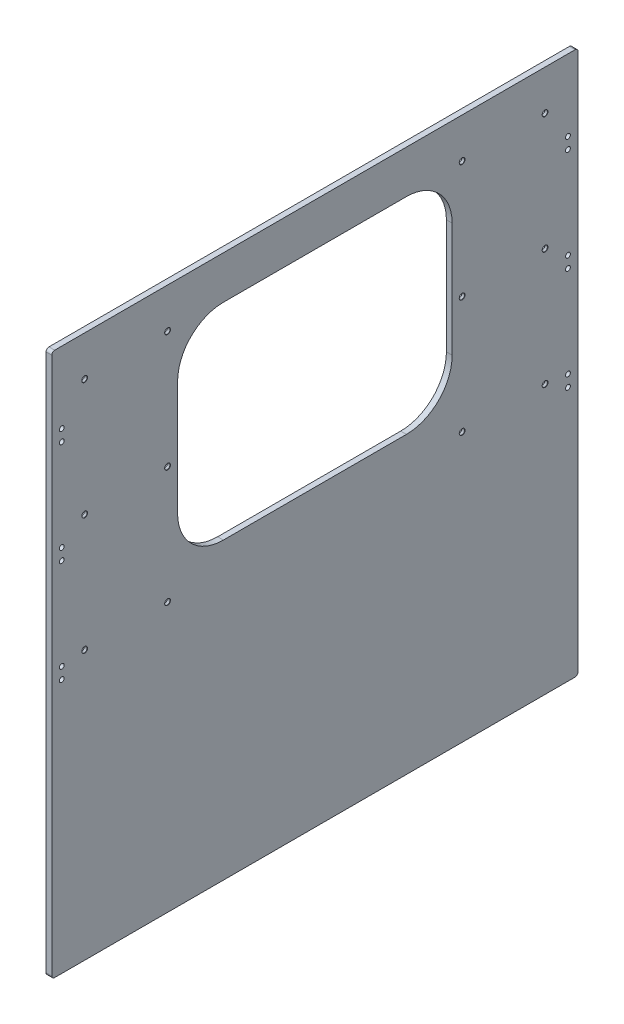
SolidWorks part; units mm, degrees
material "PE High Density"
ref_plane "Front Plane" through (0, 0, 0) normal (0, 0, 1) x (1, 0, 0)
ref_plane "Top Plane" through (0, 0, 0) normal (0, 1, 0) x (1, 0, 0)
ref_plane "Right Plane" through (0, 0, 0) normal (1, 0, 0) x (0, 0, -1)
sketch "Sketch1" plane through (0, 0, 0) normal (1, 0, 0) x (0, 0, -1)
  line L0 (6.35, 0) -> (1162.05, 0)
  line L1 (0, 6.35) -> (0, 1200.15)
  line L2 (1168.4, 6.35) -> (1168.4, 1200.15)
  line L3 (6.35, 1206.5) -> (1162.05, 1206.5)
  line L4 (381, 1111.25) -> (787.4, 1111.25)
  line L5 (279.4, 1009.65) -> (279.4, 755.65)
  line L6 (889, 1009.65) -> (889, 755.65)
  line L7 (381, 654.05) -> (787.4, 654.05)
  line L8 (279.4, 755.65) -> (0, 755.65) construction
  line L9 (889, 755.65) -> (1168.4, 755.65) construction
  arc A0 (0, 6.35) -> (6.35, 0) centre (6.35, 6.35) ccw
  arc A1 (1162.05, 0) -> (1168.4, 6.35) centre (1162.05, 6.35) ccw
  arc A2 (1168.4, 1200.15) -> (1162.05, 1206.5) centre (1162.05, 1200.15) ccw
  arc A3 (6.35, 1206.5) -> (0, 1200.15) centre (6.35, 1200.15) ccw
  arc A4 (279.4, 755.65) -> (381, 654.05) centre (381, 755.65) ccw
  arc A5 (889, 755.65) -> (787.4, 654.05) centre (787.4, 755.65) cw
  arc A6 (787.4, 1111.25) -> (889, 1009.65) centre (787.4, 1009.65) cw
  arc A7 (279.4, 1009.65) -> (381, 1111.25) centre (381, 1009.65) cw
  point P11 (0, 0)
  point P14 (1168.4, 0)
  point P17 (1168.4, 1206.5)
  point P20 (0, 1206.5)
  point P23 (279.4, 654.05)
  point P28 (889, 1111.25)
  point P31 (279.4, 1111.25)
  dimension "D7" = 6.35
  dimension "D8" = 101.6
  dimension "D1" = 1168.4
  dimension "D2" = 609.6
  dimension "D4" = 1206.5
  dimension "D5" = 654.05
  dimension "D6" = 457.2
extrude "Boss-Extrude1" add sketch "Sketch1" along normal blind 12.7
hole_wizard "CSK for 1/4 Flat Head Machine Screw1" positions "Sketch2" profile "Sketch3" countersink size "1/4" standard "ANSI Inch" end condition through all
sketch "Sketch2" plane through (12.7, 0, 0) normal (1, 0, 0) x (0, 0, -1)
  line L3 (1162.05, 1206.5) -> (6.35, 1206.5) construction
  line L4 (279.4, 1009.65) -> (279.4, 755.65) construction
  line L5 (889, 755.65) -> (889, 1009.65) construction
  point P0 (73.025, 1117.6)
  point P2 (73.025, 857.25)
  point P4 (73.025, 596.9)
  point P6 (257.175, 1117.6)
  point P8 (257.175, 857.25)
  point P10 (257.175, 596.9)
  point P12 (911.225, 1117.6)
  point P14 (911.225, 857.25)
  point P16 (911.225, 596.9)
  point P18 (1095.375, 1117.6)
  point P20 (1095.375, 857.25)
  point P22 (1095.375, 596.9)
  dimension "D1" = 184.15
  dimension "D2" = 184.15
  dimension "D3" = 22.225
  dimension "D4" = 22.225
  dimension "D5" = 88.9
  dimension "D6" = 260.35
  dimension "D7" = 260.35
sketch "Sketch3" plane through (12.7, 1117.6, -73.025) normal (0, 1, 0) x (0, 0, -1)
  line L0 (0, 0) -> (0, 12.7)
  line L1 (0, 12.7) -> (3.3782, 12.7)
  line L2 (3.3782, 12.7) -> (3.3782, 4.5369)
  line L3 (3.3782, 4.5369) -> (6.4389, 1.016)
  line L4 (6.4389, 1.016) -> (6.4389, 0)
  line L6 (6.4389, 0) -> (0, 0)
  line L7 (-3.3782, 4.5369) -> (-6.4389, 1.016) construction
  line L11 (0, -6.35) -> (0, 107.95) construction
  dimension "Thru Hole Dia." = 6.7564
  dimension "Thru Hole Depth" = 12.7
  dimension "C'Sink Dia." = 12.8778
  dimension "C'Sink Angle" = 82
  dimension "Head Clearance" = 1.016
hole_wizard "27/64 (0.42188) Diameter Hole1" positions "Sketch4" profile "Sketch5" hole size "27/64" standard "ANSI Inch" end condition through all
sketch "Sketch4" plane through (12.7, 0, 0) normal (1, 0, 0) x (0, 0, -1)
  line L0 (0, 1200.15) -> (0, 6.35) construction
  line L1 (1168.4, 6.35) -> (1168.4, 1200.15) construction
  line L2 (1162.05, 1206.5) -> (6.35, 1206.5) construction
  point P0 (22.225, 1047.75)
  point P2 (22.225, 590.55)
  point P4 (1146.175, 1047.75)
  point P6 (1146.175, 590.55)
  point P8 (1146.175, 819.15)
  point P10 (22.225, 819.15)
  point P24 (22.225, 1022.35)
  point P26 (22.225, 793.75)
  point P28 (22.225, 565.15)
  point P30 (1146.175, 1022.35)
  point P32 (1146.175, 793.75)
  point P34 (1146.175, 565.15)
  point P37 (0, 0)
  point P38 (0, 0)
  point P39 (0, 0)
  point P40 (0, 0)
  point P41 (0, 0)
  point P42 (0, 0)
  point P43 (0, 0)
  dimension "D1" = 228.6
  dimension "D2" = 228.6
  dimension "D3" = 22.225
  dimension "D4" = 22.225
  dimension "D5" = 158.75
  dimension "D6" = 25.4
  dimension "D7" = 25.4
  dimension "D8" = 25.4
sketch "Sketch5" plane through (12.7, 1047.75, -22.225) normal (0, 1, 0) x (0, 0, -1)
  line L0 (0, 0) -> (0, 12.7)
  line L1 (0, 12.7) -> (5.3579, 12.7)
  line L2 (5.3579, 12.7) -> (5.3579, 0)
  line L5 (5.3579, 0) -> (0, 0)
  line L11 (0, -6.35) -> (0, 107.95) construction
  dimension "Thru Hole Dia." = 10.7158
  dimension "Thru Hole Depth" = 12.7
